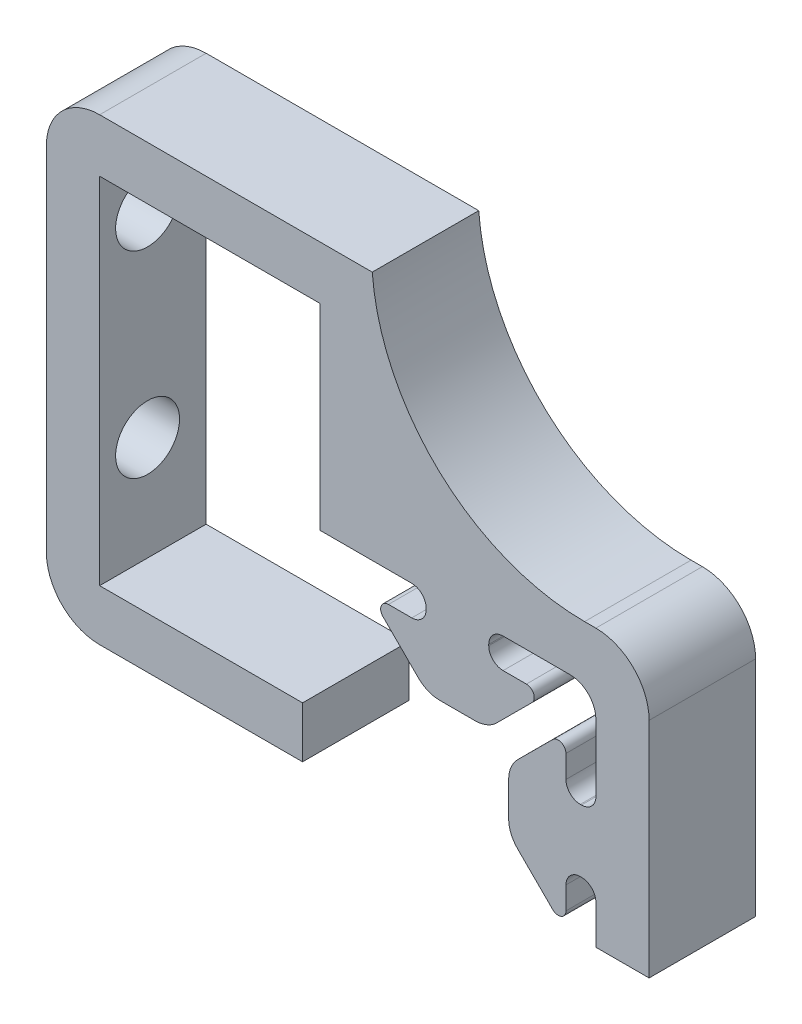
SolidWorks part; units mm, degrees
ref_plane "Front Plane" through (0, 0, 0) normal (0, 0, 1) x (1, 0, 0)
ref_plane "Top Plane" through (0, 0, 0) normal (0, 1, 0) x (1, 0, 0)
ref_plane "Right Plane" through (0, 0, 0) normal (1, 0, 0) x (0, 0, -1)
sketch "Sketch1" plane through (0, 0, 0) normal (0, 0, 1) x (1, 0, 0)
  line L1 (-4.3059, -13) -> (-4.2875, -13)
  line L11 (13, -7.9544) -> (13, -5.3171)
  line L12 (13, -5.3171) -> (13, -4.2875)
  line L13 (11.651, -2.9385) -> (11.5392, -2.9385)
  line L14 (10.1902, -4.2875) -> (10.1902, -6.4021)
  line L15 (8.949, -6.917) -> (5.6529, -3.6284)
  line L16 (4.8085, -1.5932) -> (4.8085, 1.5932)
  line L17 (5.6529, 3.6284) -> (8.949, 6.917)
  line L18 (10.1902, 6.4021) -> (10.1902, 4.2875)
  line L19 (11.5392, 2.9385) -> (11.651, 2.9385)
  line L20 (13, 4.2875) -> (13, 5.3171)
  line L21 (13, 7.9544) -> (13, 10.5918)
  line L22 (10.5918, 13) -> (5.3216, 13)
  line L23 (5.3216, 13) -> (4.2875, 13)
  line L24 (2.9385, 11.651) -> (2.9385, 11.5392)
  line L25 (4.2875, 10.1902) -> (6.4768, 10.1902)
  line L26 (6.9951, 8.9367) -> (3.6864, 5.6355)
  line L27 (1.6558, 4.7958) -> (-1.6558, 4.7958)
  line L28 (-3.6864, 5.6355) -> (-6.9951, 8.9367)
  line L29 (-6.4768, 10.1902) -> (-4.2875, 10.1902)
  line L30 (-2.9385, 11.5392) -> (-2.9385, 11.651)
  line L31 (-4.2875, 13) -> (-4.3059, 13)
  line L32 (-4.3059, 13) -> (-12.9, 13)
  line L33 (-13, 10.5918) -> (-13, 5.3171) construction
  line L34 (-13, 5.3171) -> (-13, 4.2875) construction
  line L35 (-11.651, 2.9385) -> (-11.5392, 2.9385) construction
  line L36 (-10.1902, 4.2875) -> (-10.1902, 6.4021) construction
  line L37 (-8.949, 6.917) -> (-5.6529, 3.6284) construction
  line L38 (-4.8085, 1.5932) -> (-4.8085, -1.5932) construction
  line L39 (-5.6529, -3.6284) -> (-8.949, -6.917) construction
  line L40 (-10.1902, -6.4021) -> (-10.1902, -4.2875) construction
  line L41 (-11.5392, -2.9385) -> (-11.651, -2.9385) construction
  line L43 (18, -7.9544) -> (18, 18)
  line L44 (13, 5.3171) -> (13, 7.9544)
  line L45 (-33.4, 31.3527) -> (-13, 31.3527) construction
  line L46 (-33.4, 31.3527) -> (-33.4, -1.6473) construction
  line L47 (-33.4, -1.6473) -> (-13, -1.6473) construction
  line L48 (-13, 31.3527) -> (-13, -1.6473) construction
  line L53 (-18, -6.6473) -> (-38.6, -6.6473)
  line L54 (-38.6, -6.6473) -> (-38.6, 36.4527)
  line L55 (-38.6, 36.4527) -> (-8, 36.4527)
  line L57 (-12.9, 31.4527) -> (-33.6, 31.4527)
  line L58 (-33.6, 31.4527) -> (-33.6, -1.8473)
  line L59 (-33.6, -1.8473) -> (-14.5421, -1.8473)
  line L61 (18, 18) -> (-8, 18)
  line L62 (-8, 18) -> (-8, 36.4527)
  line L63 (13, -7.9544) -> (18, -7.9544)
  line L64 (-12.9, 31.4527) -> (-12.9, 13)
  line L65 (-4.3059, 13) -> (-10.5918, 13) construction
  line L66 (-18, -6.6473) -> (-14.5421, -6.6473)
  line L67 (-14.5421, -6.6473) -> (-14.5421, -1.8473)
  line L68 (13, -10.5918) -> (13, -5.3171) construction
  line L88 (-7.1797, -8.6452) -> (-3.9523, -5.4237) construction
  line L89 (-1.7093, -4.4958) -> (1.7093, -4.4958) construction
  line L90 (3.9523, -5.4237) -> (7.1797, -8.6452) construction
  line L91 (6.4164, -10.4902) -> (4.2875, -10.4902) construction
  line L92 (3.2385, -11.5392) -> (3.2385, -11.651) construction
  line L93 (4.2875, -12.7) -> (5.3216, -12.7) construction
  line L94 (5.3216, -12.7) -> (10.5918, -12.7) construction
  line L95 (12.7, -10.5918) -> (12.7, -5.3171) construction
  line L96 (12.7, -5.3171) -> (12.7, -4.2875) construction
  line L97 (11.651, -3.2385) -> (11.5392, -3.2385) construction
  line L98 (10.4902, -4.2875) -> (10.4902, -6.4021) construction
  line L99 (8.7371, -7.1294) -> (5.441, -3.8408) construction
  line L100 (4.5085, -1.5932) -> (4.5085, 1.5932) construction
  line L101 (5.441, 3.8408) -> (8.7371, 7.1294) construction
  line L102 (10.4902, 6.4021) -> (10.4902, 4.2875) construction
  line L103 (11.5392, 3.2385) -> (11.651, 3.2385) construction
  line L104 (12.7, 4.2875) -> (12.7, 5.3171) construction
  line L105 (12.7, 5.3171) -> (12.7, 10.5918) construction
  line L106 (10.5918, 12.7) -> (5.3216, 12.7) construction
  line L107 (5.3216, 12.7) -> (4.2875, 12.7) construction
  line L108 (3.2385, 11.651) -> (3.2385, 11.5392) construction
  line L109 (4.2875, 10.4902) -> (6.4768, 10.4902) construction
  line L110 (7.207, 8.7244) -> (3.8983, 5.4232) construction
  line L111 (1.6558, 4.4958) -> (-1.6558, 4.4958) construction
  line L112 (-3.8983, 5.4232) -> (-7.207, 8.7244) construction
  line L113 (-6.4768, 10.4902) -> (-4.2875, 10.4902) construction
  line L114 (-3.2385, 11.5392) -> (-3.2385, 11.651) construction
  line L115 (-4.2875, 12.7) -> (-4.3059, 12.7) construction
  line L116 (-4.3059, 12.7) -> (-10.5918, 12.7) construction
  line L117 (-12.7, 10.5918) -> (-12.7, 5.3171) construction
  line L118 (-12.7, 5.3171) -> (-12.7, 4.2875) construction
  line L119 (-11.651, 3.2385) -> (-11.5392, 3.2385) construction
  line L120 (-10.4902, 4.2875) -> (-10.4902, 6.4021) construction
  line L121 (-8.7371, 7.1294) -> (-5.441, 3.8408) construction
  line L122 (-4.5085, 1.5932) -> (-4.5085, -1.5932) construction
  line L123 (-5.441, -3.8408) -> (-8.7371, -7.1294) construction
  line L124 (-10.4902, -6.4021) -> (-10.4902, -4.2875) construction
  line L125 (-11.5392, -3.2385) -> (-11.651, -3.2385) construction
  line L126 (-12.7, -4.2875) -> (-12.7, -5.3171) construction
  line L127 (-12.7, -5.3171) -> (-12.7, -10.5918) construction
  line L128 (-10.5918, -12.7) -> (-4.3059, -12.7) construction
  line L129 (-4.3059, -12.7) -> (-4.2875, -12.7) construction
  line L130 (-3.2385, -11.651) -> (-3.2385, -11.5392) construction
  line L131 (-4.2875, -10.4902) -> (-6.4164, -10.4902) construction
  line L132 (-13, -4.2875) -> (-13, -5.3171) construction
  line L133 (-13, -5.3171) -> (-13, -10.5918) construction
  line L134 (-10.5918, -13) -> (-4.3059, -13) construction
  line L135 (-4.2875, -10.1902) -> (-6.4164, -10.1902) construction
  line L136 (-6.9677, -8.8575) -> (-3.7403, -5.636) construction
  line L137 (-1.7093, -4.7958) -> (1.7093, -4.7958) construction
  line L138 (3.7403, -5.636) -> (6.9677, -8.8575) construction
  line L139 (6.4164, -10.1902) -> (4.2875, -10.1902) construction
  line L140 (2.9385, -11.5392) -> (2.9385, -11.651) construction
  line L141 (4.2875, -13) -> (5.3216, -13) construction
  line L142 (5.3216, -13) -> (10.5918, -13) construction
  line L143 (-2.9385, -11.651) -> (-2.9385, -11.5392) construction
  line L144 (13, 5.3171) -> (13, 10.5918) construction
  arc A4 (-1.7093, -4.7958) -> (-3.7403, -5.636) centre (-1.7093, -7.6708) ccw
  arc A9 (13, -4.2875) -> (11.651, -2.9385) centre (11.651, -4.2875) ccw
  arc A10 (11.5392, -2.9385) -> (10.1902, -4.2875) centre (11.5392, -4.2875) ccw
  arc A11 (8.949, -6.917) -> (10.1902, -6.4021) centre (9.4628, -6.4021) ccw
  arc A12 (4.8085, -1.5932) -> (5.6529, -3.6284) centre (7.6835, -1.5932) ccw
  arc A13 (5.6529, 3.6284) -> (4.8085, 1.5932) centre (7.6835, 1.5932) ccw
  arc A14 (10.1902, 6.4021) -> (8.949, 6.917) centre (9.4628, 6.4021) ccw
  arc A15 (10.1902, 4.2875) -> (11.5392, 2.9385) centre (11.5392, 4.2875) ccw
  arc A16 (11.651, 2.9385) -> (13, 4.2875) centre (11.651, 4.2875) ccw
  arc A17 (4.2875, 13) -> (2.9385, 11.651) centre (4.2875, 11.651) ccw
  arc A18 (2.9385, 11.5392) -> (4.2875, 10.1902) centre (4.2875, 11.5392) ccw
  arc A19 (6.9951, 8.9367) -> (6.4768, 10.1902) centre (6.4768, 9.4563) ccw
  arc A20 (1.6558, 4.7958) -> (3.6864, 5.6355) centre (1.6558, 7.6708) ccw
  arc A21 (-3.6864, 5.6355) -> (-1.6558, 4.7958) centre (-1.6558, 7.6708) ccw
  arc A22 (-6.4768, 10.1902) -> (-6.9951, 8.9367) centre (-6.4768, 9.4563) ccw
  arc A23 (-4.2875, 10.1902) -> (-2.9385, 11.5392) centre (-4.2875, 11.5392) ccw
  arc A24 (-2.9385, 11.651) -> (-4.2875, 13) centre (-4.2875, 11.651) ccw
  arc A25 (-13, 4.2875) -> (-11.651, 2.9385) centre (-11.651, 4.2875) ccw construction
  arc A26 (-11.5392, 2.9385) -> (-10.1902, 4.2875) centre (-11.5392, 4.2875) ccw construction
  arc A27 (-8.949, 6.917) -> (-10.1902, 6.4021) centre (-9.4628, 6.4021) ccw construction
  arc A28 (-4.8085, 1.5932) -> (-5.6529, 3.6284) centre (-7.6835, 1.5932) ccw construction
  arc A29 (-5.6529, -3.6284) -> (-4.8085, -1.5932) centre (-7.6835, -1.5932) ccw construction
  arc A30 (-10.1902, -6.4021) -> (-8.949, -6.917) centre (-9.4628, -6.4021) ccw construction
  arc A31 (-10.1902, -4.2875) -> (-11.5392, -2.9385) centre (-11.5392, -4.2875) ccw construction
  arc A32 (-11.651, -2.9385) -> (-13, -4.2875) centre (-11.651, -4.2875) ccw construction
  arc A34 (13, 10.5918) -> (10.5628, 12.9998) centre (10.5918, 10.5918) ccw
  arc A35 (-10.5628, 12.9998) -> (-12.9998, 10.5628) centre (-10.5918, 10.5918) ccw construction
  arc A37 (12.9998, 10.5628) -> (10.5628, 12.9998) centre (10.5918, 10.5918) ccw construction
  arc A104 (-7.1797, -8.6452) -> (-6.4164, -10.4902) centre (-6.4164, -9.4098) ccw construction
  arc A105 (-1.7093, -4.4958) -> (-3.9523, -5.4237) centre (-1.7093, -7.6708) ccw construction
  arc A106 (3.9523, -5.4237) -> (1.7093, -4.4958) centre (1.7093, -7.6708) ccw construction
  arc A107 (6.4164, -10.4902) -> (7.1797, -8.6452) centre (6.4164, -9.4098) ccw construction
  arc A108 (4.2875, -10.4902) -> (3.2385, -11.5392) centre (4.2875, -11.5392) ccw construction
  arc A109 (3.2385, -11.651) -> (4.2875, -12.7) centre (4.2875, -11.651) ccw construction
  arc A112 (10.5664, -12.6998) -> (12.6998, -10.5664) centre (10.5918, -10.5918) ccw construction
  arc A115 (12.7, -4.2875) -> (11.651, -3.2385) centre (11.651, -4.2875) ccw construction
  arc A116 (11.5392, -3.2385) -> (10.4902, -4.2875) centre (11.5392, -4.2875) ccw construction
  arc A117 (8.7371, -7.1294) -> (10.4902, -6.4021) centre (9.4628, -6.4021) ccw construction
  arc A118 (4.5085, -1.5932) -> (5.441, -3.8408) centre (7.6835, -1.5932) ccw construction
  arc A119 (5.441, 3.8408) -> (4.5085, 1.5932) centre (7.6835, 1.5932) ccw construction
  arc A120 (10.4902, 6.4021) -> (8.7371, 7.1294) centre (9.4628, 6.4021) ccw construction
  arc A121 (10.4902, 4.2875) -> (11.5392, 3.2385) centre (11.5392, 4.2875) ccw construction
  arc A122 (11.651, 3.2385) -> (12.7, 4.2875) centre (11.651, 4.2875) ccw construction
  arc A125 (12.6998, 10.5664) -> (10.5664, 12.6998) centre (10.5918, 10.5918) ccw construction
  arc A128 (4.2875, 12.7) -> (3.2385, 11.651) centre (4.2875, 11.651) ccw construction
  arc A129 (3.2385, 11.5392) -> (4.2875, 10.4902) centre (4.2875, 11.5392) ccw construction
  arc A130 (7.207, 8.7244) -> (6.4768, 10.4902) centre (6.4768, 9.4563) ccw construction
  arc A131 (1.6558, 4.4958) -> (3.8983, 5.4232) centre (1.6558, 7.6708) ccw construction
  arc A132 (-3.8983, 5.4232) -> (-1.6558, 4.4958) centre (-1.6558, 7.6708) ccw construction
  arc A133 (-6.4768, 10.4902) -> (-7.207, 8.7244) centre (-6.4768, 9.4563) ccw construction
  arc A134 (-4.2875, 10.4902) -> (-3.2385, 11.5392) centre (-4.2875, 11.5392) ccw construction
  arc A135 (-3.2385, 11.651) -> (-4.2875, 12.7) centre (-4.2875, 11.651) ccw construction
  arc A138 (-10.5664, 12.6998) -> (-12.6998, 10.5664) centre (-10.5918, 10.5918) ccw construction
  arc A141 (-12.7, 4.2875) -> (-11.651, 3.2385) centre (-11.651, 4.2875) ccw construction
  arc A142 (-11.5392, 3.2385) -> (-10.4902, 4.2875) centre (-11.5392, 4.2875) ccw construction
  arc A143 (-8.7371, 7.1294) -> (-10.4902, 6.4021) centre (-9.4628, 6.4021) ccw construction
  arc A144 (-4.5085, 1.5932) -> (-5.441, 3.8408) centre (-7.6835, 1.5932) ccw construction
  arc A145 (-5.441, -3.8408) -> (-4.5085, -1.5932) centre (-7.6835, -1.5932) ccw construction
  arc A146 (-10.4902, -6.4021) -> (-8.7371, -7.1294) centre (-9.4628, -6.4021) ccw construction
  arc A147 (-10.4902, -4.2875) -> (-11.5392, -3.2385) centre (-11.5392, -4.2875) ccw construction
  arc A148 (-11.651, -3.2385) -> (-12.7, -4.2875) centre (-11.651, -4.2875) ccw construction
  arc A151 (-12.6998, -10.5664) -> (-10.5918, -12.7) centre (-10.5918, -10.5918) ccw construction
  arc A154 (-4.2875, -12.7) -> (-3.2385, -11.651) centre (-4.2875, -11.651) ccw construction
  arc A155 (-3.2385, -11.5392) -> (-4.2875, -10.4902) centre (-4.2875, -11.5392) ccw construction
  arc A156 (-4.2875, -13) -> (-2.9385, -11.651) centre (-4.2875, -11.651) ccw construction
  arc A157 (-2.9385, -11.5392) -> (-4.2875, -10.1902) centre (-4.2875, -11.5392) ccw construction
  arc A158 (-6.9677, -8.8575) -> (-6.4164, -10.1902) centre (-6.4164, -9.4098) ccw construction
  arc A159 (3.7403, -5.636) -> (1.7093, -4.7958) centre (1.7093, -7.6708) ccw construction
  arc A160 (6.4164, -10.1902) -> (6.9677, -8.8575) centre (6.4164, -9.4098) ccw construction
  arc A161 (4.2875, -10.1902) -> (2.9385, -11.5392) centre (4.2875, -11.5392) ccw construction
  arc A162 (2.9385, -11.651) -> (4.2875, -13) centre (4.2875, -11.651) ccw construction
  dimension "D2" = 33
  dimension "D3" = 20.4
  dimension "D4" = 5
  dimension "D5" = 5
  dimension "D6" = 5
  dimension "D7" = 0.2
  dimension "D9" = 5
  dimension "D10" = 5
  dimension "D11" = 5
  dimension "D12" = 0.2
  dimension "D13" = 0.2
  dimension ".2" = 0.2
  dimension "D1" = 0.3
extrude "Boss-Extrude1" add sketch "Sketch1" along normal blind 10 contours L59 L58 L57 L55 L54 L53 L44 L20 A16 L19 A15 L18 A14 L17 A13 L16 A12 L15 A11 L14 A10 L13 A9 L12 L11 A4 region at (-11.6511, 13.3006, 0)
sketch "Sketch2" plane through (-38.6, 0, 0) normal (-1, 0, 0) x (0, 0, 1)
  line L0 (0, -6.6473) -> (0, 36.4527) construction
  line L3 (4.5, 29.4527) -> (4.5, 26.4527) construction
  line L4 (10, 31.4527) -> (0, 31.4527) construction
  line L5 (4.5, 10.9527) -> (4.5, 4.9527) construction
  line L6 (4.5, 26.4527) -> (4.5, 23.4527) construction
  circle A0 centre (4.5, 26.4527) radius 3
  circle A1 centre (4.5, 7.9527) radius 3
  dimension "D1" = 6
  dimension "D3" = 6
  dimension "D2" = 5
  dimension "D4" = 12.5
  dimension "D5" = 4.5
extrude "Cut-Extrude1" cut sketch "Sketch2" against normal up to next
fillet "Fillet1" radius 20 1 edges at (-8, 18, 5)
fillet "Fillet2" radius 5 3 edges at (-38.6, -6.6473, 5) (18, 18, 5) (-38.6, 36.4527, 5)
mirror "Mirror1" about plane through (0, 0, 0) normal (0, 0, 1) of bodies 102
sketch "Sketch3" plane through (-38.6, 0, 0) normal (-1, 0, 0) x (0, 0, 1)
  line L1 (0, 49.9999) -> (29.852, 49.9999)
  line L2 (29.852, 49.9999) -> (29.852, -34.6676)
  line L3 (29.852, -34.6676) -> (0, -34.6676)
  line L5 (0, 49.9999) -> (0, -34.6676)
extrude "Cut-Extrude2" cut sketch "Sketch3" against normal blind 125
